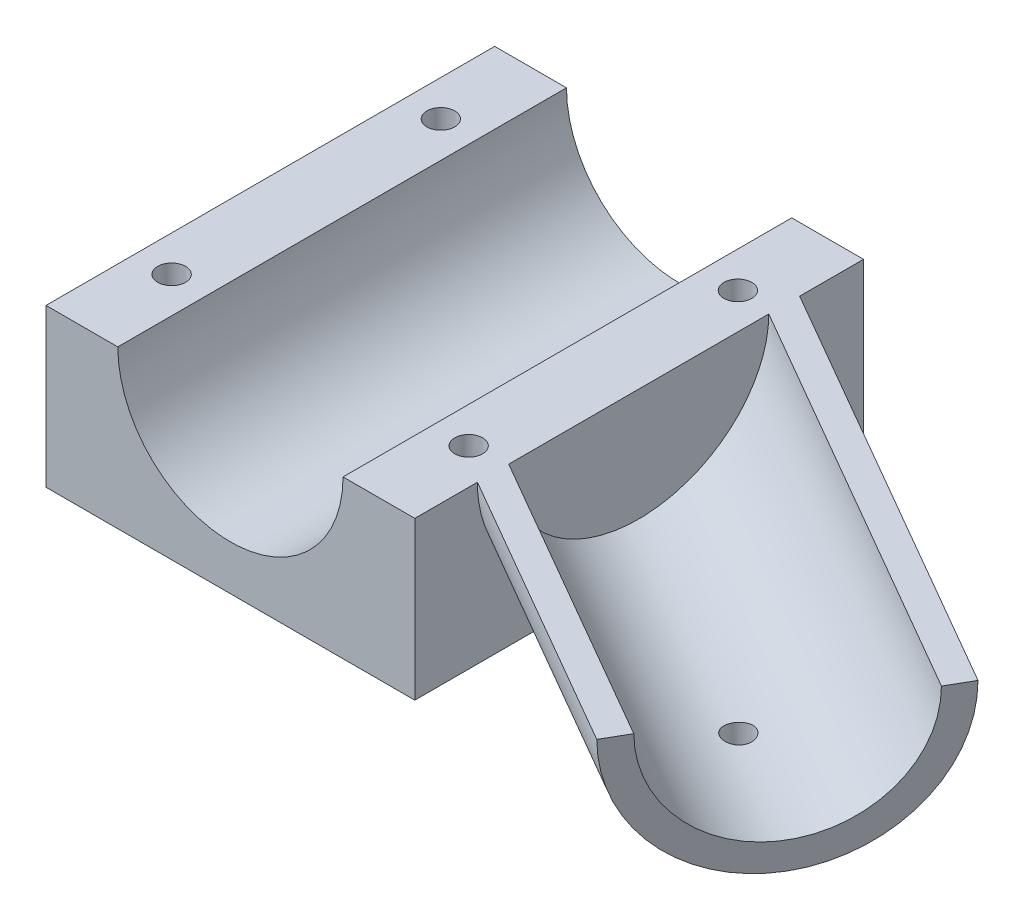
SolidWorks part; units mm, degrees
material "PLA"
ref_plane "Front Plane" through (0, 0, 0) normal (0, 0, 1) x (1, 0, 0)
ref_plane "Top Plane" through (0, 0, 0) normal (0, 1, 0) x (1, 0, 0)
ref_plane "Right Plane" through (0, 0, 0) normal (1, 0, 0) x (0, 0, -1)
sketch "Sketch1" plane through (0, 0, 0) normal (0, 0, 1) x (1, 0, 0)
  line L0 (-20.55, 17.55) -> (-20.55, 0)
  line L1 (55, 0) -> (-55, 0) construction
  line L2 (-20.55, 0) -> (20.55, 0)
  line L3 (20.55, 0) -> (20.55, 17.55)
  line L4 (-20.55, 17.55) -> (-12.55, 17.55)
  line L5 (20.55, 17.55) -> (12.55, 17.55)
  line L6 (0, -44.7868) -> (0, 44.7868) construction
  arc A0 (-12.55, 17.55) -> (12.55, 17.55) centre (0, 17.55) ccw
  dimension "D1" = 12.55
  dimension "D2" = 17.55
  dimension "D3" = 8
extrude "Boss-Extrude1" add sketch "Sketch1" along normal mid plane 50
sketch "Sketch2" plane through (0, 17.55, 0) normal (0, 1, 0) x (1, 0, 0)
  line L0 (-12.55, 25) -> (-20.55, 25) construction
  line L1 (-20.55, -25) -> (-20.55, 25) construction
  line L2 (12.55, -25) -> (12.55, 25) construction
  circle A0 centre (-16.55, 15) radius 1.55
  circle A1 centre (16.55, 15) radius 1.55
  circle A2 centre (16.55, -15) radius 1.55
  circle A3 centre (-16.55, -15) radius 1.55
  dimension "D1" = 3.1
  dimension "D2" = 30
  dimension "D3" = 10
  dimension "D4" = 4
  dimension "D5" = 4
extrude "Cut-Extrude1" cut sketch "Sketch2" against normal up to surface (17.55 mm away) up to face at (0, 0, 0)
sketch "Sketch4" plane through (0, 0, 0) normal (0, 1, 0) x (1, 0, 0)
  line L0 (20.4704, 0) -> (47.173, -15.4168) construction
  line L1 (-44.2539, 0) -> (44.2539, 0) construction
  line L2 (38.779, 0.8779) -> (28.8644, -16.2947) construction
  point P6 (33.8217, -7.7084)
  point P7 (33.8217, -7.7084)
  dimension "D1" = 30
ref_plane "LegBuildPlane" through (28.7041, 0, 16.5723) normal (0.866, 0, 0.5) x (0.5, 0, -0.866)
sketch "Sketch5" plane through (28.7041, 0, 16.5723) normal (0.866, 0, 0.5) x (0.5, 0, -0.866)
  line L0 (-5.3346, 17.55) -> (-2.3148, 17.55)
  line L1 (22.7852, 17.55) -> (25.7654, 17.55)
  line L2 (20.1498, 0) -> (0.3206, 0) construction
  arc A0 (-2.3148, 17.55) -> (22.7852, 17.55) centre (10.2352, 17.55) ccw
  arc A1 (-5.3346, 17.55) -> (25.7654, 17.55) centre (10.2154, 17.55) ccw
  point P9 (10.2352, 0)
  dimension "D1" = 15.55
  dimension "D2" = 12.55
  dimension "D3" = 17.55
  dimension "D4" = 0
extrude "Boss-Extrude2" add sketch "Sketch5" against normal up to surface and the other way blind 30 up to face at (20.55, 8.775, 0)
sketch "Sketch7" plane through (0, 17.55, 0) normal (0, 1, 0) x (1, 0, 0)
  line L0 (20.4704, 0) -> (47.173, -15.4168) construction
  line L1 (53.5274, -33.577) -> (66.0774, -11.8398) construction
  circle A0 centre (46.8121, -15.2084) radius 1.55
  dimension "D1" = 3.1
  dimension "D2" = 15
extrude "Cut-Extrude2" cut sketch "Sketch7" against normal up to surface (15.5317 mm away) up to face at (40.1713, 9.775, 11.3972)
equation "\"TubeDiam\" = 12.55"
equation "\"D1@Sketch1\"=\"TubeDiam\""
equation "\"D2@Sketch1\"=\"TubeDiam\"+5"
equation "\"MountLength\"=50"
equation "\"D1@Boss-Extrude1\"=\"MountLength\""
equation "\"MountHoleSize\"=3.1"
equation "\"D1@Sketch2\"=\"MountHoleSize\""
equation "\"D2@Sketch2\"=\"MountLength\"-20"
equation "\"LipWidth\"=8"
equation "\"D3@Sketch1\"=\"LipWidth\""
equation "\"D4@Sketch2\"=\"LipWidth\"/2"
equation "\"D5@Sketch2\"=\"LipWidth\"/2"
equation "\"LegDiam\"=12.55"
equation "\"D1@Sketch5\"=\"LegDiam\"+3"
equation "\"D2@Sketch5\"=\"TubeDiam\""
equation "\"D3@Sketch5\"=\"TubeDiam\"+5"
equation "\"D1@Sketch7\"=\"MountHoleSize\""
